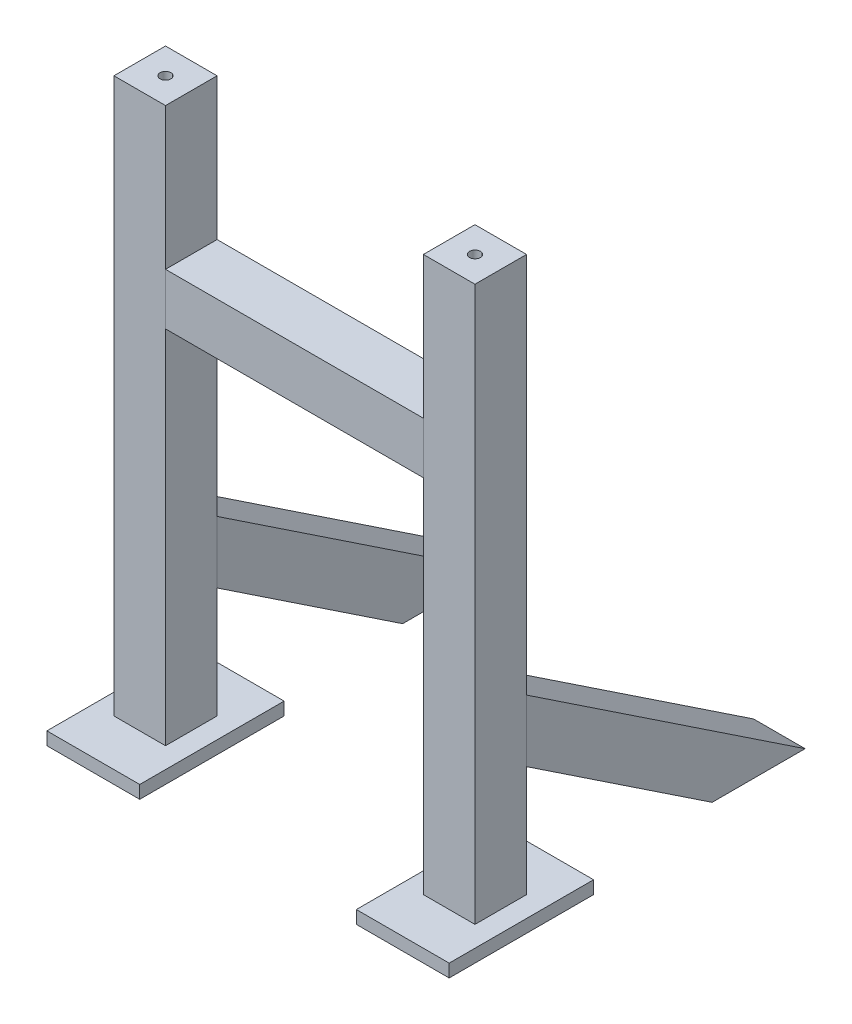
SolidWorks part; units mm, degrees
ref_plane "Front Plane" through (0, 0, 0) normal (0, 0, 1) x (1, 0, 0)
ref_plane "Top Plane" through (0, 0, 0) normal (0, 1, 0) x (1, 0, 0)
ref_plane "Right Plane" through (0, 0, 0) normal (1, 0, 0) x (0, 0, -1)
sketch "SK_FootPlates" plane through (0, 0, 0) normal (0, 1, 0) x (1, 0, 0)
  line L1 (42, 28) -> (78, 28)
  line L2 (42, 28) -> (42, -28)
  line L3 (42, -28) -> (78, -28)
  line L4 (78, 28) -> (78, -28)
  line L6 (-42, 28) -> (-78, 28)
  line L7 (-42, 28) -> (-42, -28)
  line L8 (-42, -28) -> (-78, -28)
  line L9 (-78, 28) -> (-78, -28)
  dimension "D1" = 56
  dimension "D2" = 36
  dimension "D3" = 28
  dimension "D4" = 42
  dimension "D5" = 56
  dimension "D6" = 36
  dimension "D7" = 28
  dimension "D8" = 42
extrude "EX_FootPlates" add sketch "SK_FootPlates" along normal blind 5 separate body
ref_plane "PL_Zp5" through (0, 5, 0) normal (0, 1, 0) x (1, 0, 0)
sketch "SK_Posts" plane through (0, 5, 0) normal (0, 1, 0) x (1, 0, 0)
  line L1 (50, 10) -> (70, 10)
  line L2 (50, 10) -> (50, -10)
  line L3 (50, -10) -> (70, -10)
  line L4 (70, 10) -> (70, -10)
  line L6 (-50, 10) -> (-70, 10)
  line L7 (-50, 10) -> (-50, -10)
  line L8 (-50, -10) -> (-70, -10)
  line L9 (-70, 10) -> (-70, -10)
  circle A0 centre (60, 0) radius 2.1
  circle A1 centre (-60, 0) radius 2.1
  dimension "D6" = 4.2
  dimension "D12" = 4.2
  dimension "D1" = 20
  dimension "D2" = 20
  dimension "D3" = 10
  dimension "D4" = 50
  dimension "D5" = 60
  dimension "D7" = 20
  dimension "D8" = 20
  dimension "D9" = 10
  dimension "D10" = 50
  dimension "D11" = 60
extrude "EX_Posts" add sketch "SK_Posts" along normal blind 215 separate body
ref_plane "PL_Ym50" through (-50, 0, 0) normal (1, 0, 0) x (0, 0, -1)
sketch "SK_Brace" plane through (-50, 0, 0) normal (1, 0, 0) x (0, 0, -1)
  line L1 (10, 145) -> (-10, 145)
  line L2 (10, 145) -> (10, 165)
  line L3 (10, 165) -> (-10, 165)
  line L4 (-10, 145) -> (-10, 165)
  circle A0 centre (0, 155) radius 2.1
  dimension "D1" = 20
  dimension "D2" = 20
  dimension "D3" = 10
  dimension "D6" = 4.2
  dimension "D4" = 145
  dimension "D5" = 155
extrude "EX_Brace" add sketch "SK_Brace" along normal blind 100 separate body
ref_plane "PL_Yp50" through (50, 0, 0) normal (1, 0, 0) x (0, 0, -1)
sketch "SK_StrutL" plane through (50, 0, 0) normal (1, 0, 0) x (0, 0, -1)
  line L0 (118.0278, 0) -> (81.9722, 0)
  line L1 (81.9722, 0) -> (10, 47.9815)
  line L2 (10, 47.9815) -> (10, 72.0185)
  line L3 (10, 72.0185) -> (118.0278, 0)
  dimension "D1" = 118.0278
  dimension "D2" = 81.9722
  dimension "D3" = 10
  dimension "D4" = 47.9815
  dimension "D5" = 10
  dimension "D6" = 72.0185
extrude "EX_StrutL" add sketch "SK_StrutL" along normal blind 20 separate body
ref_plane "PL_Ym70" through (-70, 0, 0) normal (1, 0, 0) x (0, 0, -1)
sketch "SK_StrutR" plane through (-70, 0, 0) normal (1, 0, 0) x (0, 0, -1)
  line L0 (118.0278, 0) -> (81.9722, 0)
  line L1 (81.9722, 0) -> (10, 47.9815)
  line L2 (10, 47.9815) -> (10, 72.0185)
  line L3 (10, 72.0185) -> (118.0278, 0)
  dimension "D1" = 118.0278
  dimension "D2" = 81.9722
  dimension "D3" = 10
  dimension "D4" = 47.9815
  dimension "D5" = 10
  dimension "D6" = 72.0185
extrude "EX_StrutR" add sketch "SK_StrutR" along normal blind 20 separate body
ref_axis "AX_X" through (0, 0, -125.3291) along (0, 0, 1)
ref_axis "AX_Y" through (85.8, 0, 0) along (-1, 0, 0)
ref_axis "AX_Z" through (0, 231, 0) along (0, -1, 0)
ref_plane "PL_Zp220" through (0, 220, 0) normal (0, 1, 0) x (1, 0, 0)
sketch "SK_F_IF_Head" plane through (0, 220, 0) normal (0, 1, 0) x (1, 0, 0)
  point P0 (0, 0)
equation "\"BODY_L\"= 420"
equation "\"BODY_W\"= 340"
equation "\"FLOOR_Z\"= 35"
equation "\"DECK_Z\"= 180"
equation "\"DECK_T\"= 2"
equation "\"GRID\"= 20"
equation "\"PROFILE\"= 20"
equation "\"SM_T\"= 1.5"
equation "\"PAN_T\"= 1.5"
equation "\"PAN_TOP\"= \"FLOOR_Z\" + \"PAN_T\""
equation "\"RAIL_Y\"= 140"
equation "\"RAIL_X\"= \"BODY_L\" / 2 - \"PROFILE\" / 2 - 2"
equation "\"BOTRING_Z\"= \"PAN_TOP\" + \"PROFILE\" / 2"
equation "\"TOPRING_Z\"= \"DECK_Z\" - \"DECK_T\" - \"PROFILE\" / 2"
equation "\"DRAWER_Z\"= 93"
equation "\"MIDX_Z\"= \"DRAWER_Z\" - \"SM_T\" - \"PROFILE\" / 2"
equation "\"SKIN_Y\"= \"RAIL_Y\" + \"PROFILE\" / 2"
equation "\"SKIN_T\"= 2"
equation "\"WHEEL_D\"= 144"
equation "\"WHEEL_W\"= 52"
equation "\"TRACK\"= 365"
equation "\"AXLE_Z\"= \"WHEEL_D\" / 2"
equation "\"WHEEL_WEB_OFF\"= 6"
equation "\"HUB_T\"= 8"
equation "\"BUSHING_L\"= 6"
equation "\"HUB_GAP\"= 1"
equation "\"MOTOR_UP\"= 7"
equation "\"MOTOR_FACE_Y\"= \"TRACK\" / 2 + \"WHEEL_WEB_OFF\" - (\"BUSHING_L\" + \"HUB_GAP\" + \"HUB_T\")"
equation "\"MOTOR_AXIS_Z\"= \"AXLE_Z\" + \"MOTOR_UP\""
equation "\"CASTER_D\"= 50"
equation "\"CASTER_X\"= 150"
equation "\"CASTER_H\"= 68"
equation "\"POST_X\"= -40"
equation "\"POST_DY\"= 120"
equation "\"POST_SIZE\"= 20"
equation "\"POST_TOP\"= 400"
equation "\"BRACE_Z\"= 335"
equation "\"STRUT_X0\"= -140"
equation "\"HEAD_X0\"= -110"
equation "\"HEAD_X1\"= 12"
equation "\"BEZEL_T\"= 3"
equation "\"WEDGE_MID\"= 7.7"
equation "\"OAK_D\"= 22.9"
equation "\"HEAD_W\"= 210"
equation "\"HEAD_Z0\"= \"POST_TOP\""
equation "\"HEAD_TOP\"= 525"
equation "\"HEAD_TOP_X\"= -20"
equation "\"SCREEN_ANG\"= 35"
equation "\"LENS_X\"= 45.6"
equation "\"LENS_Z\"= 450"
equation "\"OAK_TILT\"= 5"
equation "\"OAK_VFOV_DEPTH\"= 79.5"
equation "\"OAK_VFOV_RGB\"= 72"
equation "\"LIDAR_X\"= 110"
equation "\"SCAN_Z\"= 260"
equation "\"STRUT_Z\"= \"SCAN_Z\" - 20"
equation "\"LIDAR_SCAN_H\"= 27.2"
equation "\"LIDAR_MOUNT_Z\"= \"SCAN_Z\" - \"LIDAR_SCAN_H\""
equation "\"ESTOP_X\"= -172.5"
equation "\"ESTOP_Y\"= -127.5"
equation "\"ESTOP_TOP\"= 225"
equation "\"BUMPER_T\"= 15"
equation "\"BUMPER_Z0\"= 40"
equation "\"BUMPER_Z1\"= 130"
equation "\"CLIFF_X\"= 218"
equation "\"CLIFF_Y\"= 105"
equation "\"CLIFF_Z\"= 72"
equation "\"CLIFF_ANG\"= 50"
equation "\"CONTACT_X\"= 216"
equation "\"CONTACT_Y\"= 64"
equation "\"CONTACT_Z\"= 30"
equation "\"DOCK_TAG_DIST\"= 250"
equation "\"DOCK_TAG_SIZE\"= 80"
equation "\"DOCK_TAG_Z\"= 400"
equation "\"BAT_L\"= 240"
equation "\"BAT_W\"= 90"
equation "\"BAT_H\"= 58"
equation "\"BAT_Z\"= \"DRAWER_Z\" + \"SM_T\""
equation "\"BAT_X\"= 0"
equation "\"PCB_L\"= 95"
equation "\"PCB_W\"= 120"
equation "\"PCB_H\"= 40"
equation "\"PCB_X\"= 62.5"
equation "\"DRV_X\"= 85"
equation "\"DRV_Y\"= 100"
equation "\"DRV_S\"= 50"
equation "\"COMPUTE_X\"= -65"
equation "\"COMPUTE_L\"= 90"
equation "\"COMPUTE_W\"= 160"
equation "\"D3@SK_FootPlates\" = 28"
equation "\"D4@SK_FootPlates\" = \"POST_DY\" / 2 - 18"
equation "\"D7@SK_FootPlates\" = 28"
equation "\"D8@SK_FootPlates\" = \"POST_DY\" / 2 - 18"
equation "\"D1@SK_Posts\" = \"PROFILE\""
equation "\"D2@SK_Posts\" = \"PROFILE\""
equation "\"D4@SK_Posts\" = abs(\"POST_DY\" / 2) - \"PROFILE\" / 2"
equation "\"D5@SK_Posts\" = abs(\"POST_DY\" / 2)"
equation "\"D7@SK_Posts\" = \"PROFILE\""
equation "\"D8@SK_Posts\" = \"PROFILE\""
equation "\"D10@SK_Posts\" = abs(\"POST_DY\" / 2) - \"PROFILE\" / 2"
equation "\"D11@SK_Posts\" = abs(\"POST_DY\" / 2)"
equation "\"D1@EX_Posts\" = \"POST_TOP\" - \"DECK_Z\" - 5"
equation "\"D1@PL_Ym50\" = \"POST_DY\" / 2 - \"PROFILE\" / 2"
equation "\"D1@SK_Brace\" = \"PROFILE\""
equation "\"D2@SK_Brace\" = \"PROFILE\""
equation "\"D4@SK_Brace\" = abs(\"BRACE_Z\" - \"DECK_Z\") - \"PROFILE\" / 2"
equation "\"D5@SK_Brace\" = abs(\"BRACE_Z\" - \"DECK_Z\")"
equation "\"D1@EX_Brace\" = \"POST_DY\" - \"PROFILE\""
equation "\"D1@PL_Yp50\" = \"POST_DY\" / 2 - \"PROFILE\" / 2"
equation "\"D1@PL_Ym70\" = \"POST_DY\" / 2 + \"PROFILE\" / 2"
equation "\"D1@PL_Zp220\" = \"POST_TOP\" - \"DECK_Z\""
